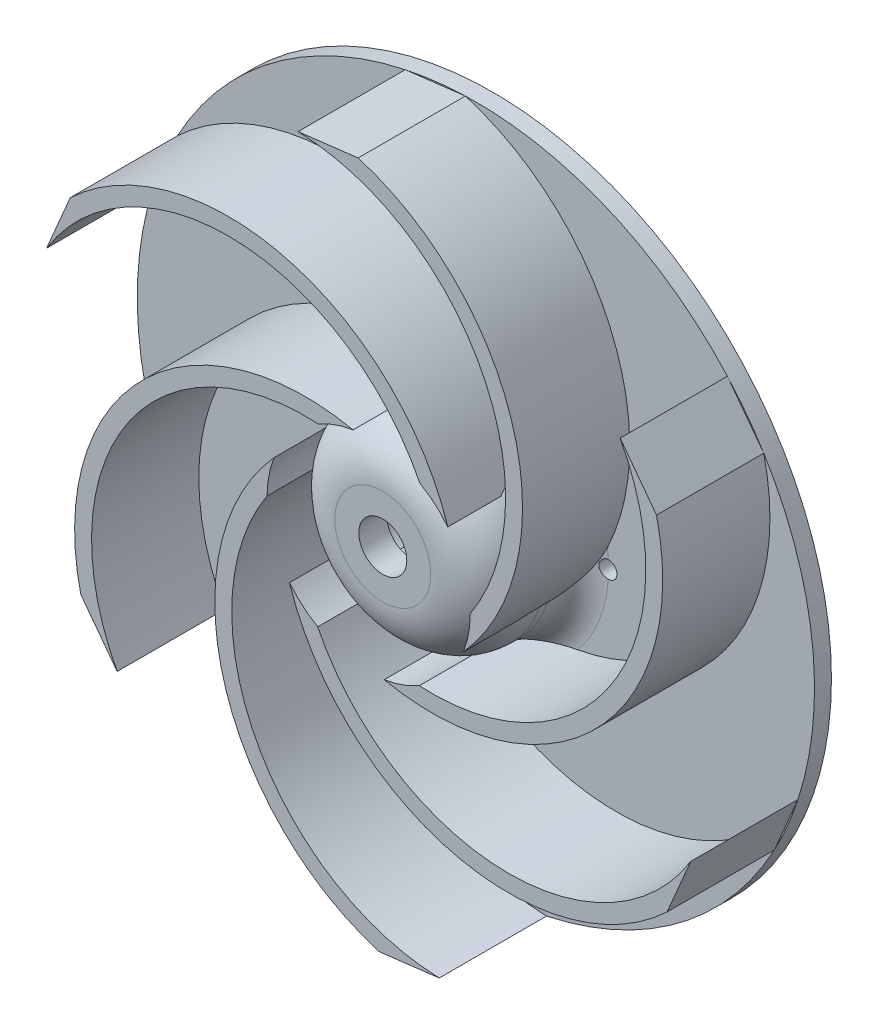
SolidWorks part; units mm, degrees
ref_plane "Alzado" through (0, 0, 0) normal (0, 0, 1) x (1, 0, 0)
ref_plane "Planta" through (0, 0, 0) normal (0, 1, 0) x (1, 0, 0)
ref_plane "Vista lateral" through (0, 0, 0) normal (1, 0, 0) x (0, 0, -1)
sketch "Croquis1" plane through (0, 0, 0) normal (0, 0, 1) x (1, 0, 0)
  circle A0 centre (0, 0) radius 60
  dimension "D1" = 120
extrude "Saliente-Extruir1" add sketch "Croquis1" along normal blind 3
sketch "Croquis2" plane through (0, 0, 0) normal (0, 0, 1) x (1, 0, 0)
  circle A0 centre (0, 0) radius 14
  dimension "D1" = 28
extrude "Cortar-Extruir2" cut sketch "Croquis2" along normal blind 1.5
sketch "Croquis3" plane through (0, 0, 0) normal (0, 0, 1) x (1, 0, 0)
  line L0 (-60, 0) -> (60, 0) construction
  circle A0 centre (0, 0) radius 60 construction
  circle A1 centre (0, 0) radius 23.5 construction
  circle A2 centre (-23.5, 0) radius 1.5
  circle A3 centre (23.5, 0) radius 1.5
  dimension "D1" = 47
  dimension "D2" = 3
  dimension "D3" = 3
extrude "Cortar-Extruir3" cut sketch "Croquis3" along normal blind 3
sketch "Croquis4" plane through (0, 0, 0) normal (0, 0, 1) x (1, 0, 0)
  circle A0 centre (0, 0) radius 44.6 construction
  circle A6 centre (0, 0) radius 4.25
  dimension "D1" = 89.2
  dimension "D2" = 8.5
extrude "Cortar-Extruir4" cut sketch "Croquis4" against normal blind 43 and the other way blind 40
sketch "Croquis5" plane through (0, 0, 1.5) normal (0, 0, -1) x (-1, 0, 0)
  line L1 (3.5, -5.45) -> (-3.5, -5.45)
  line L3 (3.5, 5.45) -> (-3.5, 5.45)
  arc A0 (-3.5, 5.45) -> (-3.5, -5.45) centre (0.1711, 0) ccw
  arc A1 (3.5, 5.45) -> (3.5, -5.45) centre (-0.1139, 0) cw
  point P0 (0, 0)
  point P6 (0, 0)
  dimension "D3" = 7
  dimension "D4" = 10.9
sketch "Croquis6" plane through (0, 0, 3) normal (0, 0, 1) x (1, 0, 0)
  circle A0 centre (0, 0) radius 18.5
  dimension "D1" = 37
extrude "Saliente-Extruir2" add sketch "Croquis6" along normal blind 16.5
extrude "Cortar-Extruir5" cut sketch "Croquis5" against normal blind 13
sketch "Croquis7" plane through (0, 0, 0) normal (0, 0, 1) x (1, 0, 0)
  circle A0 centre (0, 0) radius 4.25
  dimension "D1" = 8.5
extrude "Cortar-Extruir6" cut sketch "Croquis7" along normal blind 27
fillet "Redondeo2" radius 5 1 edges at (18.5, 0, 3)
fillet "Redondeo3" radius 10 1 edges at (18.5, 0, 19.5)
sketch "Croquis8" plane through (0, 0, 3) normal (0, 0, 1) x (1, 0, 0)
  line L0 (0, 18.5) -> (-57.0767, 18.5) construction
  line L1 (-23.67, -2.2876) -> (-22.1276, -0.6055) construction
  line L3 (-44.5598, -40.1799) -> (-51.0056, -31.5979)
  line L4 (-57.0767, 18.5) -> (-52.8674, 28.3733)
  line L5 (-12.5169, 58.6799) -> (-1.8617, 59.9711)
  line L6 (44.5598, 40.1799) -> (51.0056, 31.5979)
  line L7 (57.0767, -18.5) -> (52.8674, -28.3733)
  line L8 (12.5169, -58.6799) -> (1.8617, -59.9711)
  circle A0 centre (0, 0) radius 60 construction
  arc A1 (-2.7555, 17.7878) -> (-8.9659, 15.6081) centre (0, 0) ccw
  circle A2 centre (-23.5, 0) radius 1.5 construction
  arc A3 (-44.5598, -40.1799) -> (-8.9659, 15.6081) centre (-11.2286, -22.1971) cw
  arc A4 (-51.0056, -31.5979) -> (-2.7555, 17.7878) centre (-11.2286, -22.1971) cw
  arc A5 (-47.2001, -41.6043) -> (-8.7867, 18.6027) centre (-11.2286, -22.1971) cw construction
  arc A6 (14.027, 11.2802) -> (9.034, 15.5687) centre (0, 0) ccw
  arc A7 (-52.8674, 28.3733) -> (14.027, 11.2802) centre (-24.8375, -1.3743) cw
  arc A8 (-57.0767, 18.5) -> (9.034, 15.5687) centre (-24.8375, -1.3743) cw
  arc A9 (16.7825, -6.5076) -> (18, -0.0393) centre (0, 0) ccw
  arc A10 (-1.8617, 59.9711) -> (16.7825, -6.5076) centre (-13.609, 20.8228) cw
  arc A11 (-12.5169, 58.6799) -> (18, -0.0393) centre (-13.609, 20.8228) cw
  arc A12 (2.7555, -17.7878) -> (8.9659, -15.6081) centre (0, 0) ccw
  arc A13 (51.0056, 31.5979) -> (2.7555, -17.7878) centre (11.2286, 22.1971) cw
  arc A14 (44.5598, 40.1799) -> (8.9659, -15.6081) centre (11.2286, 22.1971) cw
  arc A15 (-14.027, -11.2802) -> (-9.034, -15.5687) centre (0, 0) ccw
  arc A16 (52.8674, -28.3733) -> (-14.027, -11.2802) centre (24.8375, 1.3743) cw
  arc A17 (57.0767, -18.5) -> (-9.034, -15.5687) centre (24.8375, 1.3743) cw
  arc A18 (-16.7825, 6.5076) -> (-18, 0.0393) centre (0, 0) ccw
  arc A19 (1.8617, -59.9711) -> (-16.7825, 6.5076) centre (13.609, -20.8228) cw
  arc A20 (12.5169, -58.6799) -> (-18, 0.0393) centre (13.609, -20.8228) cw
  circle A21 centre (0, 0) radius 18.5 construction
  circle A22 centre (0, 0) radius 18.5 construction
  circle A23 centre (0, 0) radius 60 construction
  point P8 (0, 0)
  point P9 (-56.7887, 19.3661)
  point P24 (-52.8674, 28.3733)
  dimension "D1" = 120
  dimension "D2" = 36
  dimension "D3" = 3
  dimension "D4" = 6
extrude "Saliente-Extruir3" add sketch "Croquis8" along normal blind 19
